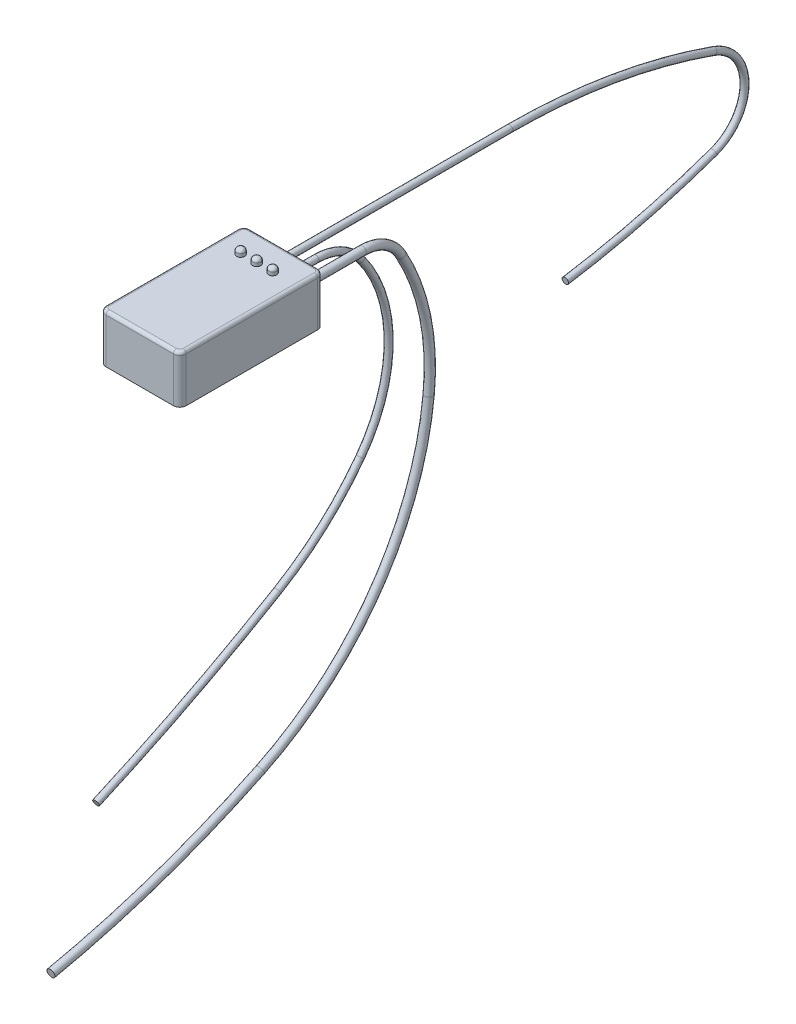
SolidWorks part; units mm, degrees
ref_plane "Alzado" through (0, 0, 0) normal (0, 0, 1) x (1, 0, 0)
ref_plane "Planta" through (0, 0, 0) normal (0, 1, 0) x (1, 0, 0)
ref_plane "Vista lateral" through (0, 0, 0) normal (1, 0, 0) x (0, 0, -1)
sketch "Croquis1" plane through (0, 0, 0) normal (0, 1, 0) x (1, 0, 0)
  line L1 (25, -45) -> (-25, -45)
  line L2 (25, -45) -> (25, 45)
  line L3 (25, 45) -> (-25, 45)
  line L4 (-25, -45) -> (-25, 45)
  line L5 (25, -45) -> (-25, 45) construction
  line L6 (25, 45) -> (-25, -45) construction
  point P0 (0, 0)
  dimension "D1" = 50
  dimension "D2" = 90
extrude "Extruir1" add sketch "Croquis1" along normal blind 30
fillet "Redondeo1" radius 4 4 edges at (25, 15, 45) (25, 15, -45) (-25, 15, 45) (-25, 15, -45)
fillet "Redondeo2" radius 2 8 edges at (-23.8284, 30, -43.8284) (0, 30, -45) (23.8284, 30, -43.8284) (25, 30, 0) (23.8284, 30, 43.8284) (0, 30, 45) (-23.8284, 30, 43.8284) (-25, 30, 0)
sketch "Croquis2" plane through (0, 30, 0) normal (0, 1, 0) x (1, 0, 0)
  line L0 (-23, 28) -> (23, 28) construction
  line L1 (-23, 41) -> (-23, -41) construction
  line L2 (23, -41) -> (23, 41) construction
  line L3 (21, 43) -> (-21, 43) construction
  circle A0 centre (0, 28) radius 2.5
  circle A1 centre (10, 28) radius 2.5
  circle A2 centre (-10, 28) radius 2.5
  dimension "D2" = 5
  dimension "D4" = 10
  dimension "D1" = 15
  dimension "D3" = 10
extrude "Extruir2" add sketch "Croquis2" along normal blind 2 separate body
dome "Cúpula1" faces to dome 1 distance 2 reverse direction no elliptical dome yes face at (-10, 32, -25.5) parameters "D1"=2
dome "Cúpula2" faces to dome 1 distance 2 reverse direction no elliptical dome yes face at (0, 32, -25.5) parameters "D1"=2
dome "Cúpula3" faces to dome 1 distance 2 reverse direction no elliptical dome yes face at (10, 32, -25.5) parameters "D1"=2
ref_plane "Plano1" through (-10, 0, 0) normal (-1, 0, 0) x (0, 0, 1)
sketch "Croquis3" plane through (-10, 0, 0) normal (-1, 0, 0) x (0, 0, 1)
  line L0 (-41, 14) -> (-195.9575, 14)
  line L1 (-41, 28) -> (-41, 0) construction
  arc A0 (-195.9575, 14) -> (-323.2973, -7.8085) centre (-195.9575, -368.6733) ccw
  arc A1 (-323.2973, -7.8085) -> (-323.2973, -62.4996) centre (-313.6478, -35.154) ccw
  arc A2 (-323.2973, -62.4996) -> (-230.7581, -85.8194) centre (-151.1605, 425.3143) ccw
ref_plane "Plano2" through (-10, 14, -41) normal (0, 0, -1) x (-1, 0, 0)
sketch "Croquis4" plane through (-10, 14, -41) normal (0, 0, -1) x (-1, 0, 0)
  circle A0 centre (0, 0) radius 2
  dimension "D1" = 4
sweep "Barrer1" add profiles "Croquis4" path "Croquis3"
ref_plane "Plano3" through (0, 0, 0) normal (-1, 0, 0) x (0, 0, 1)
sketch "Croquis5" plane through (0, 0, 0) normal (-1, 0, 0) x (0, 0, 1)
  line L0 (-41, 14) -> (-64.9605, 14)
  line L1 (-41, 14) -> (-195.9575, 14) construction
  arc A0 (-64.9605, 14) -> (-92.7811, 0) centre (-64.9605, -20.6424) ccw
  arc A1 (-92.7811, 0) -> (-92.7811, -106.9004) centre (-20.744, -53.4502) ccw
  arc A2 (-92.7811, -106.9004) -> (-41, -153.5735) centre (48.8948, -1.7795) ccw
  arc A3 (-41, -153.5735) -> (72.2697, -211.6568) centre (492.305, 746.951) ccw
sketch "Croquis6" plane through (-10, 14, -41) normal (0, 0, -1) x (-1, 0, 0)
  circle A0 centre (-10, 0) radius 2
  dimension "D1" = 4
sweep "Barrer2" add profiles "Croquis6" path "Croquis5"
ref_plane "Plano4" through (10, 0, 0) normal (-1, 0, 0) x (0, 0, 1)
sketch "Croquis7" plane through (10, 0, 0) normal (-1, 0, 0) x (0, 0, 1)
  line L0 (-41, 14) -> (-83.9744, 14)
  line L1 (-41, 14) -> (-195.9575, 14) construction
  arc A0 (-83.9744, 14) -> (-107.8558, 0) centre (-83.9744, -13.3686) ccw
  arc A1 (-107.8558, 0) -> (-125.4208, -84.5104) centre (17.3912, -70.1124) ccw
  arc A2 (-125.4208, -84.5104) -> (-20.2737, -234.9874) centre (61.8466, -65.6305) ccw
  arc A3 (-20.2737, -234.9874) -> (110.419, -279.728) centre (228.0374, 277.1052) ccw
sketch "Croquis8" plane through (-10, 14, -41) normal (0, 0, -1) x (-1, 0, 0)
  circle A0 centre (-20, 0) radius 2.5
  dimension "D1" = 5
sweep "Barrer3" add profiles "Croquis8" path "Croquis7"
